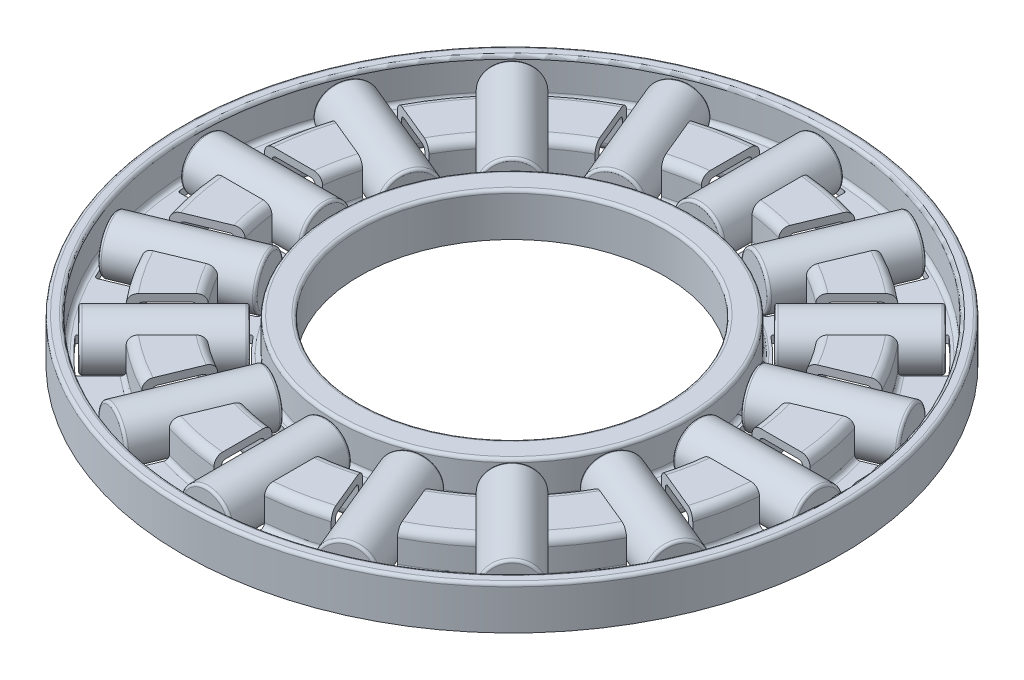
SolidWorks part; units mm, degrees
ref_plane "Front Plane" through (0, 0, 0) normal (0, 0, 1) x (1, 0, 0)
ref_plane "Top Plane" through (0, 0, 0) normal (0, 1, 0) x (1, 0, 0)
ref_plane "Right Plane" through (0, 0, 0) normal (1, 0, 0) x (0, 0, -1)
sketch "Sketch1" plane through (0, 0, 0) normal (1, 0, 0) x (0, 0, -1)
  line L0 (-13, 0) -> (13, 0) construction
  line L1 (-6.016, 0) -> (6.016, 0) construction
  line L2 (13, -1) -> (13, 1) construction
  line L3 (6.016, -0.85) -> (6.016, 0.85) construction
  line L4 (6.016, -0.85) -> (6.344, -0.85) construction
  line L5 (6.344, -0.85) -> (6.344, 0.5578) construction
  line L6 (6.344, 0.5578) -> (6.672, 0.5578) construction
  line L7 (6.672, 0.5578) -> (6.672, -0.85) construction
  line L8 (6.672, -0.85) -> (8.8232, -0.85) construction
  line L9 (8.8232, -0.85) -> (8.8232, 0.5578) construction
  line L10 (8.8232, 0.5578) -> (10.5155, 0.5578) construction
  line L11 (10.5155, 0.5578) -> (10.5155, -0.85) construction
  line L12 (10.5155, -0.85) -> (12.6667, -0.85) construction
  line L13 (12.6667, -0.85) -> (12.6667, 0.5578) construction
  line L14 (12.6667, 0.5578) -> (12.8333, 0.5578) construction
  line L15 (6.016, 0.85) -> (7, 0.85) construction
  line L16 (7, 0.85) -> (7, -0.5578) construction
  line L17 (7, -0.5578) -> (8.531, -0.5578) construction
  line L18 (8.531, -0.5578) -> (8.531, 0.85) construction
  line L19 (8.531, 0.85) -> (10.8077, 0.85) construction
  line L20 (10.8077, 0.85) -> (10.8077, -0.5578) construction
  line L21 (10.8077, -0.5578) -> (12.5, -0.5578) construction
  line L22 (12.5, -0.5578) -> (12.5, 0.85) construction
  line L23 (12.5, 0.85) -> (13, 0.85) construction
  line L24 (8.8232, 0.5578) -> (8.531, 0.5578) construction
  line L25 (6.672, 0.5578) -> (6.672, 0.85) construction
  line L26 (10.5155, 0.5578) -> (10.8077, 0.5578) construction
  line L27 (7, -0.5578) -> (7, -0.85) construction
  line L28 (7, -0.5578) -> (6.672, -0.5578) construction
  line L29 (12.6667, 0.5578) -> (12.5, 0.5578) construction
  line L30 (12.8333, 0.5578) -> (12.8333, -0.85) construction
  line L31 (12.8333, -0.85) -> (13, -0.85) construction
  line L32 (0, 1) -> (0, -1) construction
  line L33 (-7, 1) -> (7, 1) construction
  line L34 (-12.5, 0.85) -> (12.5, 0.85) construction
  line L35 (12.8333, 0.5578) -> (13, 0.5578) construction
  line L36 (8.531, -0.5578) -> (8.531, -0.85) construction
  line L37 (10.5155, 0.5578) -> (10.5155, 0.85) construction
  line L38 (6.344, -0.5578) -> (6.016, -0.5578) construction
  line L39 (6.672, -0.5578) -> (6.344, -0.5578) construction
  point P4 (0, 0)
  point P8 (0, 0)
  point P11 (13, 0)
  point P14 (6.016, 0)
  point P45 (0, 1)
  point P48 (0, 0)
  point P49 (0, 1)
  point P55 (0, 0.85)
  dimension "OD" = 26
  dimension "ID" = 12.032
  dimension "Thickness" = 2
  dimension "Approx. Raceway Thickness" = 1.7
  dimension "Inner Raceway" = 14
  dimension "Outer Raceway" = 25
  dimension "Approx. Raceway Notch Width" = 1.6923
  dimension "D3" = 1.6923
sketch "Sketch2" plane through (0, 0, 0) normal (0, 1, 0) x (1, 0, 0)
  line L0 (7, 0) -> (12.5, 0) construction
  line L1 (12.225, 0) -> (7.275, 0)
  line L2 (12.184, -1) -> (7.2059, -1)
  line L3 (12.184, 1) -> (7.2059, 1)
  circle A0 centre (0, 0) radius 6.016
  circle A1 centre (0, 0) radius 7
  circle A2 centre (0, 0) radius 12.5
  circle A3 centre (0, 0) radius 13
  arc A4 (7.2059, -1) -> (7.2059, 1) centre (0, 0) ccw
  arc A5 (12.184, -1) -> (12.184, 1) centre (0, 0) ccw
  arc A6 (12.184, 1) -> (11.905, 2.7786) centre (0, 0) ccw
  point P15 (9.75, 0)
  dimension "Approx. Roller Length" = 4.95
  dimension "Roller Thickness" = 2
  dimension "Roller Arc Length" = 2.0022
  dimension "Approx. Roller Gap" = 1.802
sketch "Sketch3" plane through (0, 0, 0) normal (1, 0, 0) x (0, 0, -1)
  line L0 (6.344, -0.85) -> (6.344, 0.5578)
  line L1 (6.344, 0.5578) -> (6.672, 0.5578)
  line L2 (6.672, 0.5578) -> (6.672, -0.85)
  line L3 (6.672, -0.85) -> (8.8232, -0.85)
  line L4 (8.8232, -0.85) -> (8.8232, 0.5578)
  line L5 (8.8232, 0.5578) -> (10.5155, 0.5578)
  line L6 (10.5155, 0.5578) -> (10.5155, -0.85)
  line L7 (10.5155, -0.85) -> (12.6667, -0.85)
  line L8 (12.6667, -0.85) -> (12.6667, 0.5578)
  line L9 (12.6667, 0.5578) -> (12.8333, 0.5578)
  line L10 (12.8333, 0.5578) -> (12.8333, -0.85)
  line L11 (12.8333, -0.85) -> (13, -0.85)
  line L12 (13, -0.85) -> (13, 0.85)
  line L13 (13, 0.85) -> (12.5, 0.85)
  line L14 (12.5, 0.85) -> (12.5, -0.5578)
  line L15 (12.5, -0.5578) -> (10.8077, -0.5578)
  line L16 (10.8077, -0.5578) -> (10.8077, 0.85)
  line L17 (10.8077, 0.85) -> (8.531, 0.85)
  line L18 (8.531, 0.85) -> (8.531, -0.5578)
  line L19 (8.531, -0.5578) -> (7, -0.5578)
  line L20 (7, -0.5578) -> (7, 0.85)
  line L21 (7, 0.85) -> (6.016, 0.85)
  line L22 (6.016, 0.85) -> (6.016, -0.85)
  line L23 (6.016, -0.85) -> (6.344, -0.85)
revolve "Revolve1" add sketch "Sketch3" angle 360 about L32
fillet "Fillet1" radius 0.3385 4 edges at (0, -0.85, 10.5155) (0, -0.85, 12.6667) (0, -0.85, 6.672) (0, -0.85, 8.8232)
fillet "Fillet2" radius 0.3385 2 edges at (0, 0.85, 10.8077) (0, 0.85, 8.531)
fillet "Fillet3" radius 0.125 4 edges at (0, 0.85, 12.5) (0, 0.85, 13) (0, 0.85, 7) (0, 0.85, 6.016)
fillet "Fillet4" radius 0.1692 6 edges at (0, 0.5578, 8.8232) (0, 0.5578, 10.5155) (0, -0.5578, 12.5) (0, -0.5578, 10.8077) (0, -0.5578, 8.531) (0, -0.5578, 7)
sketch "Sketch4" plane through (0, 0, 0) normal (0, 1, 0) x (1, 0, 0)
  line L0 (7.2059, 1) -> (12.184, 1)
  line L1 (7.2059, -1) -> (12.184, -1)
  arc A0 (7.2059, -1) -> (7.2059, 1) centre (0, 0) ccw construction
  arc A1 (7.2059, -1) -> (7.2059, 1) centre (0, 0) ccw
  arc A2 (12.184, -1) -> (12.184, 1) centre (0, 0) ccw construction
  arc A3 (12.184, -1) -> (12.184, 1) centre (0, 0) ccw
extrude "Cut-Extrude1" cut sketch "Sketch4" against normal through all both and the other way through all
fillet "Fillet5" radius 0.1001 4 edges at (12.184, -0.7039, -1) (12.184, -0.7039, 1) (7.2059, -0.7039, -1) (7.2059, -0.7039, 1)
pattern_circular "CirPattern1" count 16 over 360 about axis through (0, 1, 0) along (0, -1, 0) of "Cut-Extrude1", "Fillet5"
sketch "Sketch5" plane through (0, 0, 0) normal (0, 1, 0) x (1, 0, 0)
  line L0 (7.32, 0) -> (7.32, 1)
  line L2 (7.32, 1) -> (12.0914, 1)
  line L3 (12.0914, 1) -> (12.0914, 0)
  line L4 (12.0914, 0) -> (7.32, 0)
  line L5 (12.225, 0) -> (7.275, 0) construction
revolve "Revolve2" add sketch "Sketch5" angle 360 about L1
fillet "Fillet6" radius 0.1001 2 edges at (7.32, 0, -1) (12.0914, 0, -1)
pattern_circular "CirPattern2" count 16 over 360 about axis through (0, 1, 0) along (0, -1, 0) of bodies 107
ref_axis "Center Axis 1" through (0, 1.65, 0) along (0, -1, 0)
ref_plane "Contact Plane 1" through (0, 1, 0) normal (0, 1, 0) x (1, 0, 0)
ref_plane "Contact Plane 2" through (0, -1, 0) normal (0, 1, 0) x (1, 0, 0)
equation "\"Approx. Raceway Thickness@Sketch1\" = \"Thickness@Sketch1\" * .85"
equation "\"Approx. Raceway Notch Width@Sketch1\" =  ( \"Outer Raceway@Sketch1\" - \"Inner Raceway@Sketch1\" )  / 6.5"
equation "\"D3@Sketch1\" = \"Approx. Raceway Notch Width@Sketch1\""
equation "\"D1@Fillet2\"=\"D1@Fillet1\""
equation "\"D1@Fillet3\"=(\"OD@Sketch1\"-\"Outer Raceway@Sketch1\")/8"
equation "\"D1@Fillet1\" = \"Approx. Raceway Notch Width@Sketch1\" * 2 / 10"
equation "\"D1@Fillet4\"=\"D1@Fillet2\"/2"
equation "\"Approx. Roller Length@Sketch2\" =  ( \"Outer Raceway@Sketch1\" - \"Inner Raceway@Sketch1\" )  / 2 * .9"
equation "\"Approx. Roller Gap@Sketch2\" = \"Roller Arc Length@Sketch2\" * .9"
equation "\"Raceway Diff\"= ( \"Outer Raceway@Sketch1\" - \"Inner Raceway@Sketch1\" )"
equation "\"Circumference\"= ( \"Inner Raceway@Sketch1\" + ( \"Raceway Diff\" / 2 ) ) * 3.14"
equation "\"Instances\"= int ( \"Circumference\" /  ( \"Roller Arc Length@Sketch2\" + \"Approx. Roller Gap@Sketch2\" )  ) "
equation "\"D1@CirPattern1\"=\"Instances\""
equation "\"D1@Fillet5\" = \"Roller Arc Length@Sketch2\" / 20"
equation "\"D1@Fillet6\" = \"Roller Arc Length@Sketch2\" / 20"
equation "\"D1@CirPattern2\" = \"D1@CirPattern1\""
equation "\"Roller Thickness@Sketch2\" = \"Thickness@Sketch1\""
